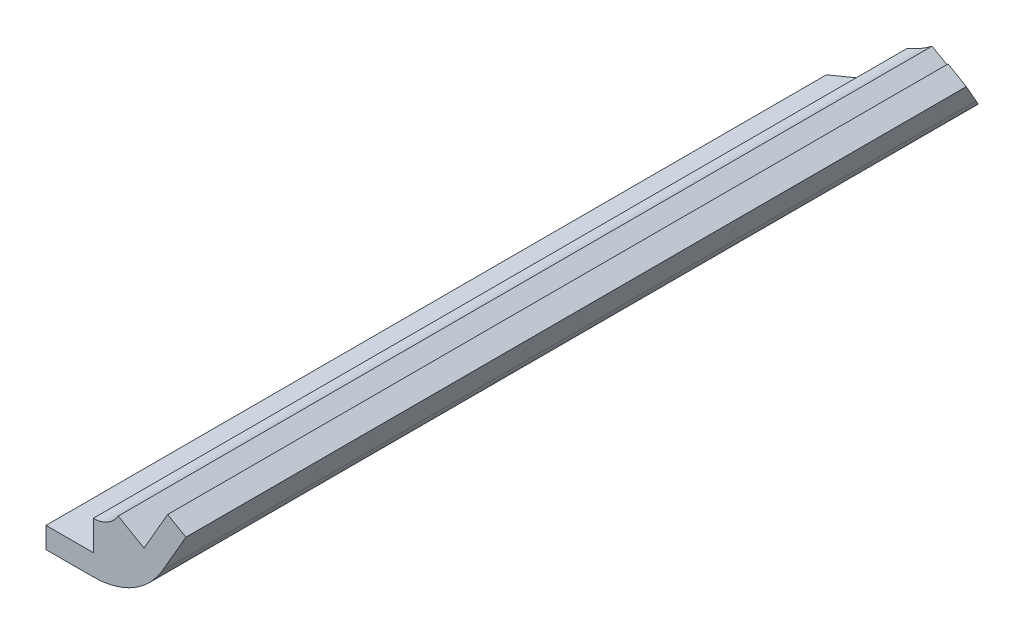
SolidWorks part; units mm, degrees
ref_plane "Front Plane" through (0, 0, 0) normal (0, 0, 1) x (1, 0, 0)
ref_plane "Top Plane" through (0, 0, 0) normal (0, 1, 0) x (1, 0, 0)
ref_plane "Right Plane" through (0, 0, 0) normal (1, 0, 0) x (0, 0, -1)
ref_axis "Axis1" through (0, 0, -88.99) along (0, 0, 1)
sketch "Sketch16" plane through (0, 0, 0) normal (0, 1, 0) x (1, 0, 0)
  line L0 (0, -127) -> (0, 127) construction
  point P2 (0, 0)
  dimension "D1" = 254
sketch "Sketch2" plane through (0, 0, 0) normal (0, 0, 1) x (1, 0, 0)
  line L0 (-7.3025, -1.5) -> (-2.54, -1.5) construction
  line L1 (-7.3025, -1.5) -> (-7.3025, 1.5) construction
  line L2 (-2.54, -1.5) -> (-2.54, 1.5) construction
  line L3 (-7.3025, 1.5) -> (-2.54, 1.5) construction
  line L4 (-2.54, 0) -> (0, 0) construction
  line L5 (0, 0) -> (1.27, 2.1997) construction
  line L6 (2.569, 1.4497) -> (-0.029, 2.9497) construction
  line L7 (2.569, 1.4497) -> (4.9503, 5.5742) construction
  line L8 (-0.029, 2.9497) -> (2.3522, 7.0742) construction
  line L9 (4.9503, 5.5742) -> (2.3522, 7.0742) construction
  point P7 (1.27, 2.1997)
  point P16 (-0.866, 1.5)
  dimension "D1" = 3
  dimension "D2" = 4.7625
  dimension "D3" = 2.54
  dimension "D4" = 120
ref_plane "Plane1" through (0, 0, 0) normal (-0.866, 0.5, 0) x (0.5, 0.866, 0)
sketch "Sketch7" plane through (0, 0, 0) normal (0, 0, 1) x (1, 0, 0)
  line L0 (-7.3025, -1.5) -> (-2.54, -1.5)
  line L1 (-7.3025, -1.5) -> (-7.3025, -3.6212)
  line L2 (-2.54, -1.5) -> (-2.54, -3.6212)
  line L3 (-7.3025, -3.6212) -> (-2.54, -3.6212)
  dimension "D1" = 2.1212
extrude "Boss-Extrude2" add sketch "Sketch7" along normal mid plane 260.35 separate body
sketch "Sketch8" plane through (0, 0, 0) normal (0, 0, 1) x (1, 0, 0)
  line L0 (2.569, 1.4497) -> (4.9503, 5.5742)
  line L1 (2.569, 1.4497) -> (4.4061, 0.3891)
  line L2 (4.9503, 5.5742) -> (6.7873, 4.5135)
  line L3 (4.4061, 0.3891) -> (6.7873, 4.5135)
  line L4 (-2.54, -3.6212) -> (-2.54, -1.5) construction
extrude "Boss-Extrude3" add sketch "Sketch8" along normal mid plane 260.35
sketch "Sketch11" plane through (0, 0, 0) normal (0, 0, 1) x (1, 0, 0)
  line L1 (-2.54, -1.5) -> (-7.3025, -1.5)
  line L2 (-7.3025, -1.5) -> (-7.3025, -3.6212)
  line L8 (6.7873, 4.5135) -> (4.9503, 5.5742)
  line L9 (4.9503, 5.5742) -> (2.569, 1.4497)
  line L13 (2.569, 1.4497) -> (-0.029, 2.9497)
  line L14 (-0.029, 2.9497) -> (-0.866, 1.5) construction
  line L15 (-0.866, 1.5) -> (-2.54, 1.5) construction
  line L17 (-2.54, 1.5) -> (-2.54, -1.5)
  line L18 (6.7873, 4.5135) -> (4.4061, 0.3891)
  line L19 (2.569, 1.4497) -> (4.4061, 0.3891) construction
  line L20 (-2.54, -3.6212) -> (-7.3025, -3.6212)
  arc A0 (-0.029, 2.9497) -> (-2.54, 1.5) centre (-2.54, 4.3994) cw
  arc A1 (4.4061, 0.3891) -> (-2.54, -3.6212) centre (-2.54, 4.3994) cw
extrude "Boss-Extrude4" add sketch "Sketch11" along normal mid plane 260.35
ref_plane "Midplane" through (0, 0, 0) normal (0.866, 0.5, 0) x (0.5, -0.866, 0)
sketch "Sketch17" plane through (0, 0, 46.4198) normal (0.4714, -0.8165, -0.3333) x (-0.6667, -0.5774, 0.4714)
  line L0 (304.8, 0) -> (0, 0)
  line L1 (-304.8, 0) -> (-152.4, -263.9645)
  line L2 (-152.4, -263.9645) -> (152.4, -263.9645) construction
  line L3 (152.4, -263.9645) -> (304.8, 0) construction
  line L4 (304.8, 0) -> (152.4, 263.9645)
  line L5 (152.4, 263.9645) -> (-152.4, 263.9645)
  line L6 (-152.4, 263.9645) -> (-304.8, 0)
  line L7 (0, 0) -> (-152.4, -263.9645)
  circle A0 centre (0, 0) radius 263.9645 construction
  dimension "D1" = 304.8
extrude "Cut-Extrude1" cut sketch "Sketch17" against normal through all both and the other way through all
equation "\"plate_thickness\"= 3mm"
equation "\"D1@Sketch2\"=\"plate_thickness\""
equation "\"joiner_lip_width\"= .1875"
equation "\"D2@Sketch2\"=\"joiner_lip_width\""
equation "\"face_gap\"=0.1"
equation "\"D3@Sketch2\"=\"face_gap\""
equation "\"inside_angle\"= 180 - arccos ( 1 / 2 )"
equation "\"joiner_thickness\"= 0.0835128"
equation "\"edge_length\"= 10"
equation "\"Face1_TopLip\"= \"angle\" * 2"
equation "\"Face1_BottomLip\"= \"angle\" * 2"
equation "\"Face2_TopLip\"= 45deg"
equation "\"Face2_BottomLip\"= 45deg"
equation "\"D1@Sketch7\"=\"joiner_thickness\""
equation "\"D1@Boss-Extrude2\"=\"Extrude_to\""
equation "\"D1@Boss-Extrude3\"=\"Extrude_to\""
equation "\"D1@Boss-Extrude4\"=\"Extrude_to\""
equation "\"Extrude_to\"= \"edge_length\" + .25"
equation "\"D1@Sketch16\"=\"edge_length\""
equation "\"angle\"= atn ( 0.1 / ( ( 3.7085 - 3.0793 ) / 2 ) )"
equation "\"D4@Sketch2\"=\"inside_angle\""
equation "\"D2@Sketch5\"=\"Face2_TopLip\"/2"
equation "\"D1@Sketch5\"=\"Face2_BottomLip\"/2"
equation "\"D2@Sketch4\"=\"Face1_TopLip\"/2"
equation "\"D1@Sketch4\"=\"Face1_BottomLip\"/2"
equation "\"D1\" = \"edge_length\""
equation "\"D2@Sketch12\"=\"Face1_TopLip\"/2"
equation "\"D1@Sketch12\"=\"Face1_BottomLip\"/2"
